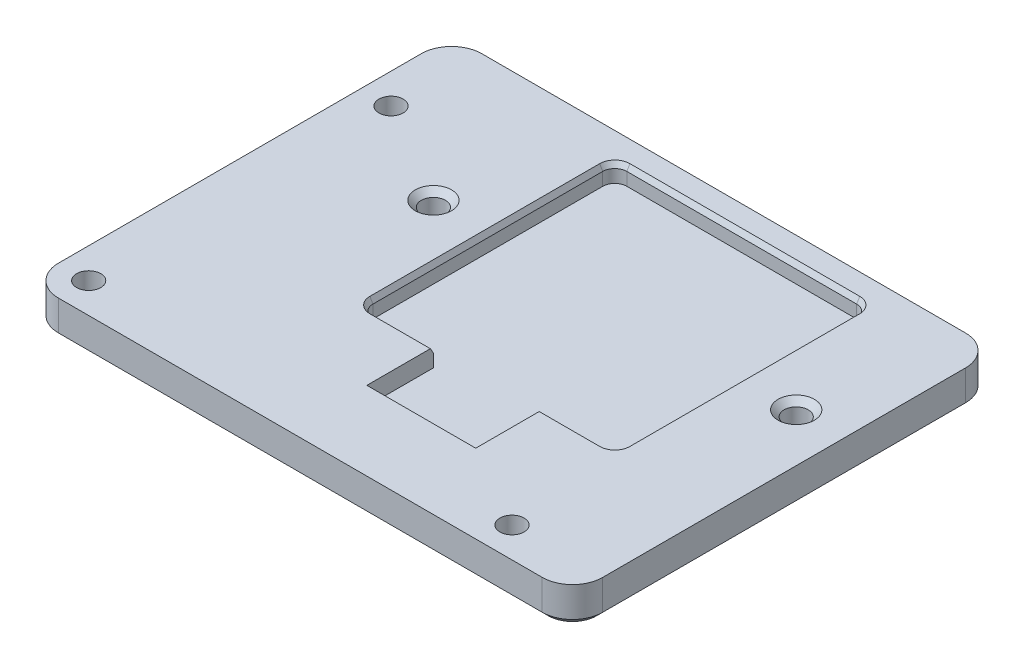
SolidWorks part; units mm, degrees
ref_plane "Спереди" through (0, 0, 0) normal (0, 0, 1) x (1, 0, 0)
ref_plane "Сверху" through (0, 0, 0) normal (0, 1, 0) x (1, 0, 0)
ref_plane "Справа" through (0, 0, 0) normal (1, 0, 0) x (0, 0, -1)
sketch "Эскиз1" plane through (0, 0, 0) normal (0, 1, 0) x (1, 0, 0)
  line L1 (-40, -30) -> (50, -30)
  line L2 (-40, -30) -> (-40, 40)
  line L3 (-40, 40) -> (50, 40)
  line L4 (50, -30) -> (50, 40)
  line L7 (-35, -25) -> (35, -25) construction
  line L8 (-35, -25) -> (-35, 25) construction
  line L9 (-35, 25) -> (35, 25) construction
  line L10 (35, -25) -> (35, 25) construction
  circle A0 centre (-35, 25) radius 2
  circle A1 centre (35, 25) radius 2
  circle A2 centre (-35, -25) radius 2
  circle A3 centre (35, -25) radius 2
  point P0 (0, 0)
  point P6 (0, 0)
  point P12 (0, 0)
  point P15 (0.1928, -0.186)
  dimension "D3" = 4
  dimension "D4" = 70
  dimension "D1" = 90
  dimension "D2" = 70
  dimension "D5" = 50
  dimension "D6" = 50
  dimension "D7" = 30
extrude "Бобышка-Вытянуть1" add sketch "Эскиз1" along normal blind 6 contours L1 L4 L3 L2 A3 A2 A1 A0 | A1 region at (5.0402, 0, -5.0402) region at (35, 0, -25)
fillet "Скругление1" radius 5 4 edges at (-40, 3, -40) (50, 3, -40) (50, 3, 30) (-40, 3, 30)
sketch "Эскиз2" plane through (0, 6, 0) normal (0, 1, 0) x (1, 0, 0)
  line L1 (-9, -6) -> (33, -6)
  line L2 (-9, -6) -> (-9, 36)
  line L3 (-9, 36) -> (33, 36)
  line L4 (33, -6) -> (33, 36)
  line L5 (12, 36) -> (12, -6) construction
  line L6 (-9, 15) -> (33, 15) construction
  circle A0 centre (35, -25) radius 2 construction
  circle A1 centre (-35, -25) radius 2 construction
  point P0 (12, 15)
  point P8 (0, 0)
  point P9 (0, 0)
  dimension "D3" = 23
  dimension "D5" = 47
  dimension "D6" = 40
  dimension "D1" = 42
  dimension "D2" = 42
  dimension "D4" = 40
extrude "Вырез-Вытянуть1" cut sketch "Эскиз2" against normal blind 3
sketch "Эскиз3" plane through (0, 6, 0) normal (0, 1, 0) x (1, 0, 0)
  line L0 (12, 36) -> (12, -32.6922) construction
  line L1 (33, 36) -> (-9, 36) construction
  line L2 (-9, -6) -> (33, -6) construction
  line L3 (3, -15) -> (21, -15)
  line L4 (3, -15) -> (3, 3)
  line L5 (3, 3) -> (21, 3)
  line L6 (21, -15) -> (21, 3)
  line L7 (12, 3) -> (12, -15) construction
  line L8 (3, -6) -> (21, -6) construction
  point P4 (12, -6)
  dimension "D1" = 18
  dimension "D2" = 18
extrude "Вырез-Вытянуть2" cut sketch "Эскиз3" against normal blind 3
fillet "Скругление2" radius 2 4 edges at (33, 4.5, 6) (-9, 4.5, 6) (-9, 4.5, -36) (33, 4.5, -36)
chamfer "Фаска1" distance 2 angle 45 1 edges at (12, 6, 15)
sketch "Эскиз4" plane through (0, 6, 0) normal (0, 1, 0) x (1, 0, 0)
  line L0 (12, 36) -> (-9, 15) construction
  line L1 (31, 36) -> (-7, 36) construction
  line L2 (-9, 34) -> (-9, -4) construction
  line L3 (-9, 15) -> (44.3239, 15) construction
  line L4 (44.3239, 15) -> (-42.5122, 15) construction
  line L5 (12, -17) -> (12, 32.404) construction
  line L6 (21, -17) -> (3, -17) construction
  circle A0 centre (-18, 15) radius 2
  circle A1 centre (42, 15) radius 2
  dimension "D1" = 30
  dimension "D2" = 4
extrude "Вырез-Вытянуть3" cut sketch "Эскиз4" against normal blind 5
chamfer "Фаска2" distance 1 angle 45 2 edges at (42, 6, -17) (-18, 6, -13)
chamfer "Фаска3" distance 1 angle 45 11 edges at (-38.5355, 0, 28.5355) (5, 0, 30) (48.5355, 0, 28.5355) (50, 0, -5) (48.5355, 0, -38.5355) (5, 0, -40) (-38.5355, 0, -38.5355) (-40, 0, -5) (-35, 0, -23) (-35, 0, 27) (35, 0, 27)
sketch "Эскиз5" plane through (0, 3, 0) normal (0, 1, 0) x (1, 0, 0)
  line L0 (12, 36) -> (12, 4.7203) construction
  line L1 (31, 36) -> (-7, 36) construction
  line L2 (12, 4.7203) -> (33, 15) construction
  line L3 (33, -4) -> (33, 34) construction
  line L4 (33, 15) -> (-10.4557, 15) construction
  circle A0 centre (12, 15) radius 5
  point P2 (0, 0)
extrude "Бобышка-Вытянуть2" [suppressed] add sketch "Эскиз5" along normal blind 100
chamfer "Фаска4" distance 0.5 angle 60 9 edges at (26, 6, 6) (32.4142, 6, 5.4142) (33, 6, -15) (32.4142, 6, -35.4142) (12, 6, -36) (-2, 6, 6) (-8.4142, 6, -35.4142) (-8.4142, 6, 5.4142) (-9, 6, -15) first distance on face at (42, 6, -12)
